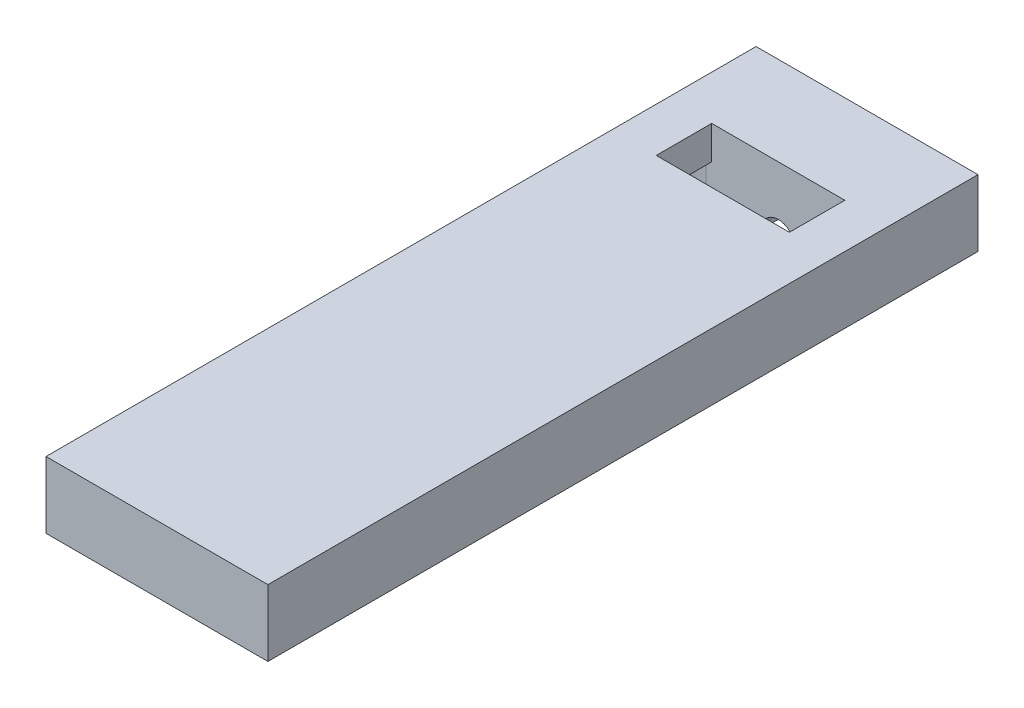
SolidWorks part; units mm, degrees
ref_plane "Front Plane" through (0, 0, 0) normal (0, 0, 1) x (1, 0, 0)
ref_plane "Top Plane" through (0, 0, 0) normal (0, 1, 0) x (1, 0, 0)
ref_plane "Right Plane" through (0, 0, 0) normal (1, 0, 0) x (0, 0, -1)
sketch "Sketch1" plane through (0, 0, 0) normal (0, 1, 0) x (1, 0, 0)
  line L1 (-31.75, -101.6) -> (31.75, -101.6)
  line L2 (-31.75, -101.6) -> (-31.75, 101.6)
  line L3 (-31.75, 101.6) -> (31.75, 101.6)
  line L4 (31.75, -101.6) -> (31.75, 101.6)
  line L5 (-31.75, -101.6) -> (31.75, 101.6) construction
  line L6 (-31.75, 101.6) -> (31.75, -101.6) construction
  point P0 (0, 0)
  dimension "D1" = 63.5
  dimension "D2" = 203.2
extrude "Boss-Extrude1" add sketch "Sketch1" along normal blind 19.05
sketch "Sketch2" plane through (0, 0, -101.6) normal (0, 0, -1) x (-1, 0, 0)
  line L1 (-31.75, 0) -> (31.75, 0) construction
  circle A0 centre (0, 0) radius 4.7625
  dimension "D1" = 9.525
extrude "Cut-Extrude1" cut sketch "Sketch2" against normal blind 25.4
ref_plane "Plane1" through (0, 0, 0) normal (0, -1, 0) x (-1, 0, 0)
sketch "Sketch3" plane through (0, 0, 0) normal (0, -1, 0) x (-1, 0, 0)
  line L0 (4.7625, 76.2) -> (-4.7625, 76.2) construction
  line L1 (-20.6375, -96.8375) -> (20.6375, -96.8375)
  line L2 (-26.9875, -90.4875) -> (-26.9875, 1.27)
  line L3 (-20.6375, 76.2) -> (20.6375, 76.2)
  line L4 (26.9875, -90.4875) -> (26.9875, 1.27)
  line L5 (20.6375, 31.75) -> (-20.6375, 31.75)
  line L6 (20.6375, 7.62) -> (-20.6375, 7.62)
  line L7 (26.9875, 38.1) -> (26.9875, 69.85)
  line L8 (-26.9875, 38.1) -> (-26.9875, 69.85)
  line L14 (4.7625, 101.6) -> (4.7625, 76.2)
  line L15 (4.7625, 76.2) -> (-4.7625, 76.2)
  line L16 (-4.7625, 76.2) -> (-4.7625, 101.6)
  line L17 (-4.7625, 101.6) -> (-31.75, 101.6)
  line L18 (-31.75, 101.6) -> (-31.75, -101.6)
  line L19 (-31.75, -101.6) -> (31.75, -101.6)
  line L20 (31.75, -101.6) -> (31.75, 101.6)
  line L21 (31.75, 101.6) -> (4.7625, 101.6)
  line L25 (-4.7625, 101.6) -> (-31.75, 101.6) construction
  line L26 (-31.75, 101.6) -> (-31.75, -101.6) construction
  line L27 (-31.75, -101.6) -> (31.75, -101.6) construction
  line L28 (31.75, -101.6) -> (31.75, 101.6) construction
  line L29 (31.75, 101.6) -> (4.7625, 101.6) construction
  arc A0 (-26.9875, -90.4875) -> (-20.6375, -96.8375) centre (-20.6375, -90.4875) ccw
  arc A1 (20.6375, -96.8375) -> (26.9875, -90.4875) centre (20.6375, -90.4875) ccw
  arc A2 (26.9875, 69.85) -> (20.6375, 76.2) centre (20.6375, 69.85) ccw
  arc A3 (-20.6375, 76.2) -> (-26.9875, 69.85) centre (-20.6375, 69.85) ccw
  arc A4 (20.6375, 7.62) -> (26.9875, 1.27) centre (20.6375, 1.27) cw
  arc A5 (-20.6375, 7.62) -> (-26.9875, 1.27) centre (-20.6375, 1.27) ccw
  arc A6 (-20.6375, 31.75) -> (-26.9875, 38.1) centre (-20.6375, 38.1) cw
  arc A7 (20.6375, 31.75) -> (26.9875, 38.1) centre (20.6375, 38.1) ccw
  point P0 (0, 0)
  point P33 (-26.9875, 31.75)
  point P36 (26.9875, 31.75)
  dimension "D5" = 6.35
  dimension "D6" = 44.45
  dimension "D8" = 6.35
  dimension "D2" = 9.525
  dimension "D3" = 9.525
  dimension "D4" = 9.525
  dimension "D7" = 24.13
  dimension "D1" = 0
extrude "Cut-Extrude2" cut sketch "Sketch3" against normal blind 9.525
sketch "Sketch4" plane through (0, 0, 0) normal (0, 1, 0) x (1, 0, 0)
  line L1 (4.7625, 101.6) -> (4.7625, 76.2) construction
  line L2 (4.7625, 76.2) -> (20.6375, 76.2) construction
  circle A0 centre (11.1125, 76.2) radius 4.7625
  dimension "D2" = 9.525
  dimension "D3" = 6.35
extrude "Cut-Extrude3" [suppressed] cut sketch "Sketch4" along normal up to next
sketch "Sketch5" plane through (0, 0, 0) normal (0, 1, 0) x (1, 0, 0)
  line L0 (4.7625, 76.2) -> (20.6375, 76.2) construction
  line L1 (19.05, 76.2) -> (-19.05, 76.2)
  line L2 (19.05, 76.2) -> (19.05, 60.325)
  line L3 (19.05, 60.325) -> (-19.05, 60.325)
  line L4 (-19.05, 76.2) -> (-19.05, 60.325)
  line L5 (0, 0) -> (0, 132.0825) construction
  dimension "D1" = 15.875
  dimension "D2" = 38.1
extrude "Cut-Extrude4" cut sketch "Sketch5" along normal through all
sketch "Sketch6" plane through (0, 0, 0) normal (0, 1, 0) x (1, 0, 0)
  line L1 (-26.9875, 38.1) -> (26.9875, 38.1)
  line L2 (-26.9875, 38.1) -> (-26.9875, 1.27)
  line L3 (-26.9875, 1.27) -> (26.9875, 1.27)
  line L4 (26.9875, 38.1) -> (26.9875, 1.27)
extrude "Cut-Extrude5" cut sketch "Sketch6" along normal blind 2.159
